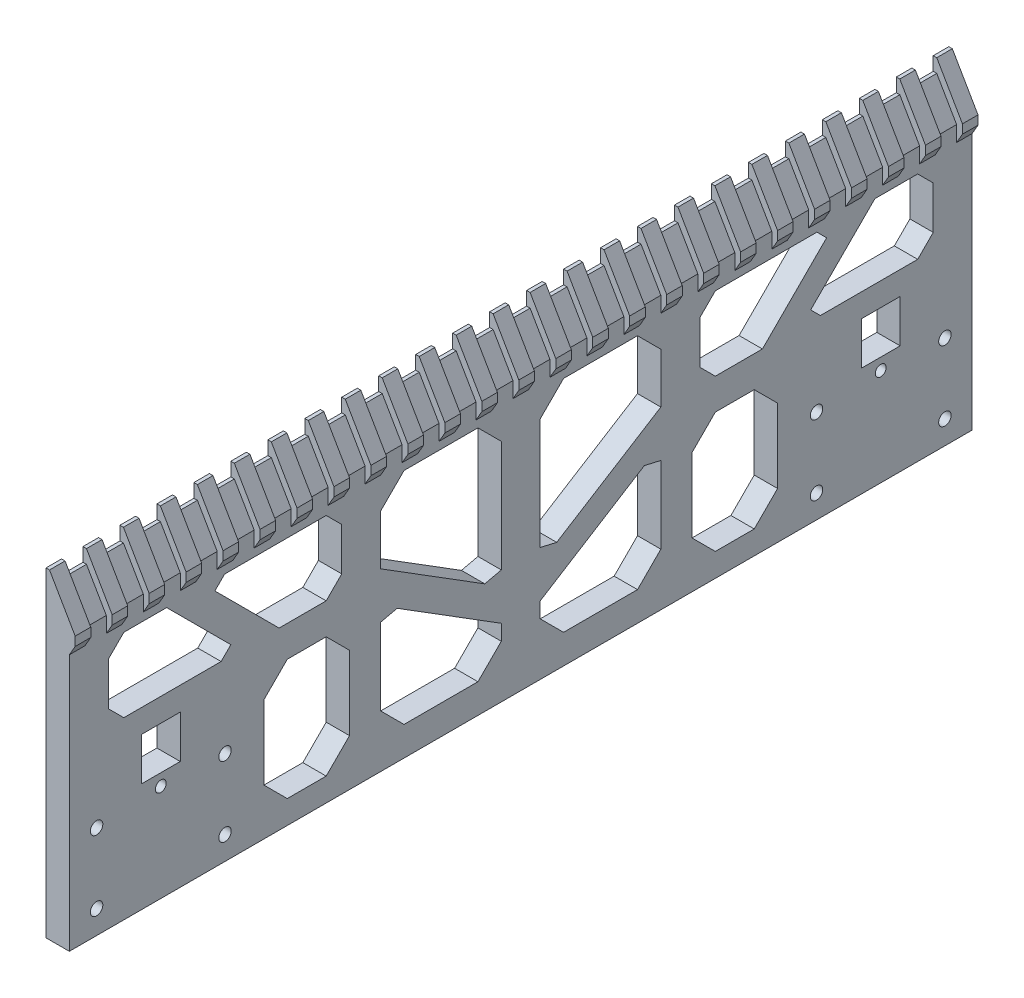
SolidWorks part; units mm, degrees
ref_plane "前视基准面" through (0, 0, 0) normal (0, 0, 1) x (1, 0, 0)
ref_plane "上视基准面" through (0, 0, 0) normal (0, 1, 0) x (1, 0, 0)
ref_plane "右视基准面" through (0, 0, 0) normal (1, 0, 0) x (0, 0, -1)
sketch "草图1" plane through (0, 0, 0) normal (1, 0, 0) x (0, 0, -1)
  line L0 (0, 0) -> (0, -70) construction
  line L1 (-116, 0) -> (116, 0)
  line L2 (-116, 0) -> (-116, -70)
  line L3 (-116, -70) -> (116, -70)
  line L4 (116, 0) -> (116, -70)
  dimension "D1" = 116
  dimension "D2" = 70
extrude "凸台-拉伸1" add sketch "草图1" along normal blind 6
sketch "草图3" plane through (6, 0, 0) normal (1, 0, 0) x (0, 0, -1)
  line L0 (0, 0) -> (0, -70) construction
  line L1 (-102, -6) -> (-91, -6)
  line L2 (-106, -10) -> (-106, -21)
  line L3 (-102, -25) -> (-72, -25)
  line L4 (-46, -10) -> (-46, -21)
  line L5 (116, 0) -> (-116, 0) construction
  line L6 (-116, -70) -> (116, -70) construction
  line L7 (-116, 0) -> (-116, -70) construction
  line L12 (-106, -10) -> (-102, -6)
  line L13 (-106, -21) -> (-102, -25)
  line L14 (-50, -25) -> (-46, -21)
  line L15 (-50, -6) -> (-46, -10)
  line L28 (-36, -12) -> (-30, -6)
  line L36 (-66, -58) -> (-60, -64)
  line L42 (-30, -6) -> (-11, -6)
  line L43 (-36, -12) -> (-36, -24.8748)
  line L44 (-30, -62.5) -> (-11, -62.5)
  line L45 (-5, -12) -> (-5, -44.2458)
  line L46 (-11, -6) -> (-5, -12)
  line L47 (-11, -62.5) -> (-5, -56.5)
  line L48 (-36, -56.5) -> (-30, -62.5)
  line L49 (-60, -33) -> (-50, -33)
  line L50 (-66, -39) -> (-66, -58)
  line L51 (-60, -64) -> (-50, -64)
  line L52 (-44, -39) -> (-44, -58)
  line L53 (-50, -64) -> (-44, -58)
  line L54 (-50, -33) -> (-44, -39)
  line L55 (-66, -39) -> (-60, -33)
  line L56 (-81.1005, -6) -> (-62.1005, -25)
  line L57 (-91, -6) -> (-72, -25)
  line L58 (-91, -6) -> (-81.1005, -6) construction
  line L59 (-81.1005, -6) -> (-50, -6)
  line L60 (-72, -25) -> (-62.1005, -25) construction
  line L61 (-62.1005, -25) -> (-50, -25)
  line L62 (-36, -24.8748) -> (-5, -44.2458)
  line L63 (-5, -52.5) -> (-36, -33.1291)
  line L64 (-5, -44.2458) -> (-5, -52.5) construction
  line L65 (-5, -52.5) -> (-5, -56.5)
  line L66 (-36, -24.8748) -> (-36, -33.1291) construction
  line L67 (-36, -33.1291) -> (-36, -56.5)
  point P0 (-106, -6)
  point P1 (-46, -25)
  point P2 (-106, -25)
  point P3 (-46, -6)
  point P20 (-36, -6)
  point P21 (-5, -62.5)
  point P22 (-36, -62.5)
  point P23 (-5, -6)
  point P24 (-66, -33)
  point P33 (-44, -64)
  point P34 (-66, -64)
  point P35 (-44, -33)
  dimension "D1" = 10
  dimension "D2" = 6
  dimension "D3" = 19
  dimension "D4" = 60
  dimension "D5" = 6
  dimension "D6" = 7.5
  dimension "D7" = 56.5
  dimension "D12" = 80
  dimension "D13" = 5
  dimension "D14" = 31
  dimension "D15" = 10
  dimension "D16" = 8
  dimension "D21" = 8
  dimension "D22" = 31
  dimension "D23" = 22
  dimension "D24" = 7
  dimension "D25" = 45
  dimension "D30" = 34
  dimension "D31" = 7
  dimension "D32" = 10
  dimension "D33" = 58
extrude "切除-拉伸2" cut sketch "草图3" against normal through all
chamfer "倒角1" distance 5 angle 45 4 edges at (3, -33.1291, 36) (3, -44.2458, 5) (3, -6, 81.1005) (3, -25, 72) first distance on face at (3, -42.8145, 20.5) first distance on face at (3, -34.5603, 20.5) first distance on face at (3, -6, 65.5503) first distance on face at (3, -25, 87)
sketch "草图2" plane through (0, 0, 0) normal (1, 0, 0) x (0, 0, -1)
  line L0 (-92.5, -26.6289) -> (-92.5, -71.7155) construction
  line L1 (-109, -46) -> (-76, -46) construction
  line L2 (-109, -46) -> (-109, -64) construction
  line L3 (-109, -64) -> (-76, -64) construction
  line L4 (-76, -46) -> (-76, -64) construction
  line L5 (116, 0) -> (-116, 0) construction
  line L6 (0, 0) -> (0, -70) construction
  circle A0 centre (-109, -46) radius 1.55
  circle A1 centre (-76, -64) radius 1.55
  circle A2 centre (-76, -46) radius 1.55
  circle A3 centre (-109, -64) radius 1.55
  point P8 (-92.5, -46)
  dimension "D5" = 3.1
  dimension "D1" = 92.5
  dimension "D2" = 46
  dimension "D3" = 33
  dimension "D4" = 18
sketch "草图6" plane through (0, 0, 116) normal (0, 0, 1) x (1, 0, 0)
  line L0 (6, 0) -> (0, 0)
  line L1 (0, 0) -> (0, 8.8335)
  line L2 (0.9, 8.8335) -> (6, 0)
  line L3 (0, 8.8335) -> (0.9, 8.8335)
  line L4 (0, 8.8335) -> (0, 10.3923) construction
  line L5 (0, 10.3923) -> (0.9, 8.8335) construction
  dimension "D1" = 30
  dimension "D2" = 0.9
extrude "凸台-拉伸2" add sketch "草图6" against normal up to surface (232 mm away) up to face at (3, -35, -116)
ref_plane "基准面1" through (0, 0, 0) normal (0, 0, -1) x (-1, 0, 0)
sketch "草图8" plane through (0, 0, 116) normal (0, 0, 1) x (1, 0, 0)
  line L0 (0, 10.3923) -> (0, 12.3335)
  line L1 (0.9, 12.3335) -> (7.5, 0.9019)
  line L2 (7.5, 0.9019) -> (7.5, -1.4019)
  line L3 (7.5, -4) -> (6, -4) construction
  line L4 (6, 0) -> (6, -70) construction
  line L5 (6, -4) -> (6, 0)
  line L6 (6, 0) -> (0.9, 8.8335) construction
  line L7 (6, 0) -> (0.9, 8.8335)
  line L8 (0, 12.3335) -> (0.9, 12.3335)
  line L9 (0, 12.3335) -> (0, 13.8923) construction
  line L10 (0, 13.8923) -> (0.9, 12.3335) construction
  line L11 (0, 10.3923) -> (0, 8.8335)
  line L12 (0, 8.8335) -> (0.9, 8.8335)
  line L13 (0.9, 8.8335) -> (0, 10.3923) construction
  line L14 (6, -4) -> (7.5, -1.4019)
  line L15 (7.5, -1.4019) -> (7.5, -4) construction
  dimension "D1" = 3.5
  dimension "D2" = 1.5
  dimension "D3" = 4
  dimension "D4" = 0.9
  dimension "D5" = 30
extrude "凸台-拉伸3" add sketch "草图8" against normal blind 4
pattern_linear "阵列(线性)1" count 25 spacing 9.5 along (0, 0, -1) of "凸台-拉伸3"
hole_wizard "打孔尺寸(%根据)内六角圆柱头螺钉的类型1" positions "草图14" profile "草图15" counterbore size "M3" standard "GB" end condition through all
sketch "草图14" plane through (0, 0, 0) normal (-1, 0, 0) x (0, 0, 1)
  point P0 (76, -46)
  point P3 (109, -46)
  point P6 (109, -64)
  point P9 (76, -64)
sketch "草图15" plane through (0, -46, 76) normal (0, 1, 0) x (0, 0, 1)
  line L0 (0, 0) -> (0, 7.5)
  line L1 (0, 7.5) -> (1.6, 7.5)
  line L3 (1.6, 7.5) -> (1.6, 3.4)
  line L4 (1.6, 3.4) -> (3, 3.4)
  line L5 (3, 3.4) -> (3, 0)
  line L7 (3, 0) -> (0, 0)
  line L11 (0, -6.35) -> (0, 107.95) construction
  dimension "通孔孔直径" = 3.2
  dimension "通孔孔深度" = 7.5
  dimension "柱形沉头孔直径" = 6
  dimension "柱形沉头孔深度" = 3.4
sketch "草图16" plane through (0, 0, 0) normal (-1, 0, 0) x (0, 0, 1)
  line L0 (109, -46) -> (76, -46) construction
  line L2 (116, -70) -> (-116, -70) construction
  line L3 (92.5, -26.6289) -> (92.5, -71.7155) construction
  circle A0 centre (92.5, -45) radius 1.4
  dimension "D1" = 2.8
  dimension "D2" = 25
extrude "切除-拉伸3" cut sketch "草图16" against normal blind 10
mirror "镜向1" about plane through (0, 0, 0) normal (0, 0, -1) of "打孔尺寸(%根据)内六角圆柱头螺钉的类型1"
mirror "镜向2" about plane through (0, 0, 0) normal (0, 0, -1) of "倒角1", "切除-拉伸2", "切除-拉伸3"
sketch "草图17" plane through (0, 0, 0) normal (-1, 0, 0) x (0, 0, 1)
  line L1 (87.5, -31) -> (97.5, -31)
  line L2 (87.5, -31) -> (87.5, -42)
  line L3 (87.5, -42) -> (97.5, -42)
  line L4 (97.5, -31) -> (97.5, -42)
  line L6 (116, -70) -> (-116, -70) construction
  line L7 (0, -70) -> (0, -8.018) construction
  line L8 (-87.5, -31) -> (-97.5, -31)
  line L9 (-87.5, -31) -> (-87.5, -42)
  line L10 (-87.5, -42) -> (-97.5, -42)
  line L11 (-97.5, -31) -> (-97.5, -42)
  line L12 (92.5, -26.6289) -> (92.5, -71.7155) construction
  line L13 (92.5, -26.6289) -> (92.5, -71.7155) construction
  dimension "D1" = 10
  dimension "D2" = 11
  dimension "D4" = 28
extrude "切除-拉伸4" cut sketch "草图17" against normal through all
